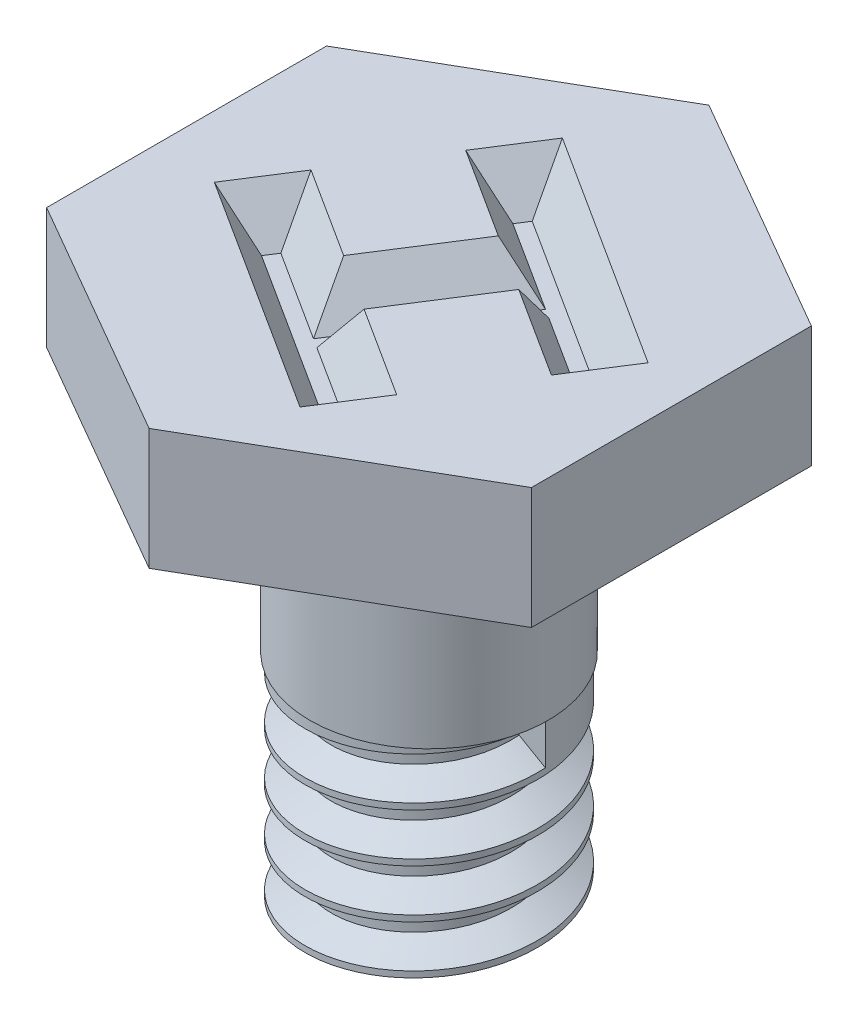
SolidWorks part; units mm, degrees
ref_plane "Front" through (0, 0, 0) normal (0, 0, 1) x (1, 0, 0)
ref_plane "Top" through (0, 0, 0) normal (0, 1, 0) x (1, 0, 0)
ref_plane "Right" through (0, 0, 0) normal (1, 0, 0) x (0, 0, -1)
sketch "Sketch1" plane through (0, 0, 0) normal (0, 1, 0) x (1, 0, 0)
  circle A0 centre (0, 0) radius 4.8
  dimension "D1" = 9.6
extrude "Boss-Extrude1" add sketch "Sketch1" along normal blind 17.5
sketch "Sketch2" plane through (0, 17.5, 0) normal (0, 1, 0) x (1, 0, 0)
  line L1 (0, 11.547) -> (-10, 5.7735)
  line L2 (-10, 5.7735) -> (-10, -5.7735)
  line L3 (-10, -5.7735) -> (0, -11.547)
  line L4 (0, -11.547) -> (10, -5.7735)
  line L5 (10, -5.7735) -> (10, 5.7735)
  line L6 (10, 5.7735) -> (0, 11.547)
  circle A0 centre (0, 0) radius 10 construction
  dimension "D1" = 20
extrude "Boss-Extrude2" add sketch "Sketch2" along normal blind 5
sketch "Sketch3" plane through (0, 22.5, 0) normal (0, 1, 0) x (1, 0, 0)
  line L0 (3.9048, -5.2376) -> (0.1743, -2.853)
  line L1 (2.3496, -7.6706) -> (3.9048, -5.2376)
  line L2 (-7.4469, -1.4084) -> (2.3496, -7.6706)
  line L3 (-5.8918, 1.0245) -> (-7.4469, -1.4084)
  line L4 (-2.1613, -1.3601) -> (-5.8918, 1.0245)
  line L5 (0.327, 2.5326) -> (-2.1613, -1.3601)
  line L6 (-3.4035, 4.9172) -> (0.327, 2.5326)
  line L7 (-1.8483, 7.3501) -> (-3.4035, 4.9172)
  line L8 (7.9482, 1.0879) -> (-1.8483, 7.3501)
  line L9 (6.3931, -1.345) -> (7.9482, 1.0879)
  line L10 (2.6626, 1.0396) -> (6.3931, -1.345)
  line L11 (0.1743, -2.853) -> (2.6626, 1.0396)
  line L12 (-0.9172, 0.5863) -> (1.4184, -0.9067) construction
extrude "Cut-Extrude1" cut sketch "Sketch3" against normal blind 2
thread "Thread1" pitch 2 method cut profile "Thread Profile1" start angle 0, offset 3, length 10, pitch 2, diameter 9.6
ref_plane "Plane1" through (4.8, -3, 0) normal (0, 0, 1) x (1, 0, 0)
sketch "Thread Profile1" plane through (4.8, -3, 0) normal (0, 0, 1) x (1, 0, 0)
  line L0 (0, 0) -> (0, 2) construction
  line L11 (0, 0) -> (0, 1.75)
  line L12 (0, 1.75) -> (-1.0825, 1.125)
  line L13 (-1.0825, 1.125) -> (-1.0825, 0.625)
  line L15 (-1.0825, 0.625) -> (0, 0)
  line L17 (-1.0825, 0.875) -> (0, 0.875) construction
  point P2 (0, 0)
  dimension "Pitch" = 2
  dimension "Profile_Angle" = 60
  dimension "Profile_Land" = 0.5
  dimension "Profile_Height" = 1.0825
chamfer "Chamfer1" distance 2 angle 30 12 edges at (2.0395, 20.5, 4.0453) (3.1272, 20.5, 6.4541) (-2.5487, 20.5, 4.5395) (-6.6694, 20.5, 0.1919) (-4.0265, 20.5, 0.1678) (-0.9172, 20.5, -0.5863) (-1.5382, 20.5, -3.7249) (-2.6259, 20.5, -6.1337) (3.05, 20.5, -4.219) (7.1706, 20.5, 0.1285) (4.5278, 20.5, 0.1527) (1.4184, 20.5, 0.9067) first distance on face at (2.0395, 21.5, 4.0453) first distance on face at (3.1272, 21.5, 6.4541) first distance on face at (-2.5487, 21.5, 4.5395) first distance on face at (-6.6694, 21.5, 0.1919) first distance on face at (-4.0265, 21.5, 0.1678) first distance on face at (-0.9172, 21.5, -0.5863) first distance on face at (-1.5382, 21.5, -3.7249) first distance on face at (-2.6259, 21.5, -6.1337) first distance on face at (3.05, 21.5, -4.219) first distance on face at (7.1706, 21.5, 0.1285) first distance on face at (4.5278, 21.5, 0.1527) first distance on face at (1.4184, 21.5, 0.9067)
sketch "Sketch6" plane through (0, 17.5, 0) normal (0, -1, 0) x (1, 0, 0)
  circle A0 centre (0, 0) radius 4.8 construction
  circle A1 centre (0, 0) radius 4.8
  circle A2 centre (0, 0) radius 4.9125
  dimension "D1" = 9.825
extrude "Boss-Extrude3" add sketch "Sketch6" along normal blind 8.75
